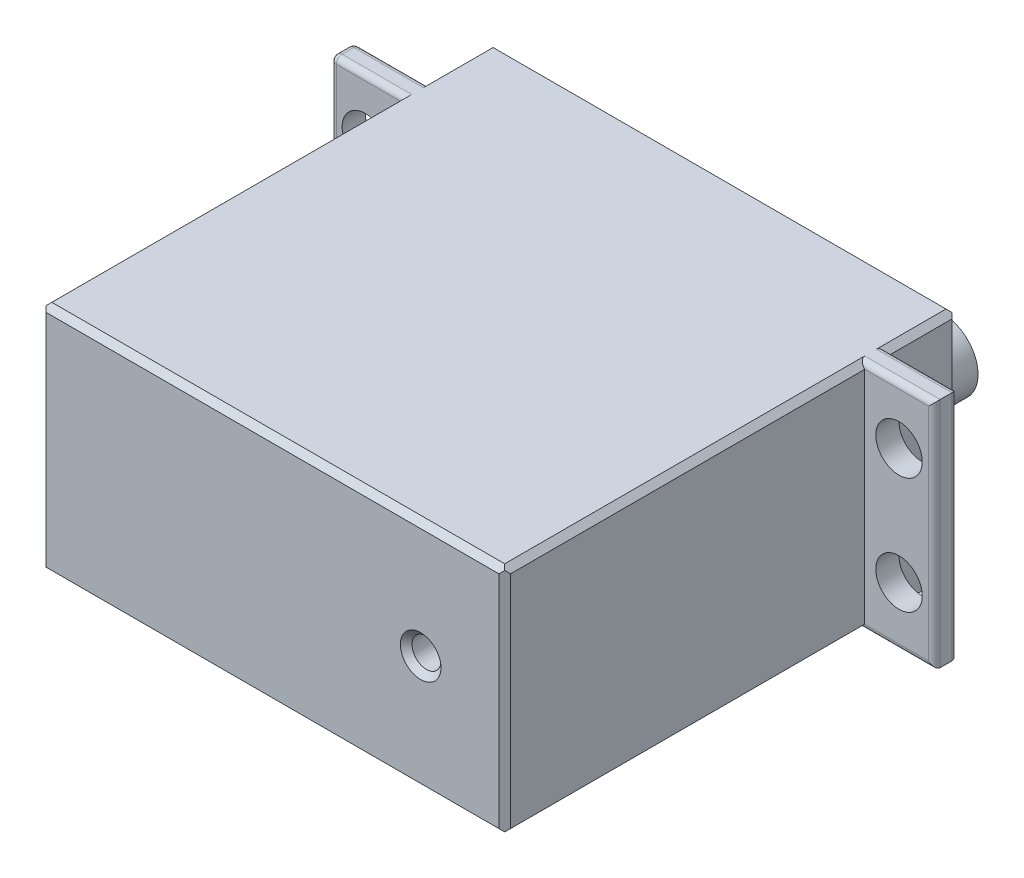
SolidWorks part; units mm, degrees
ref_plane "前视基准面" through (0, 0, 0) normal (0, 0, 1) x (1, 0, 0)
ref_plane "上视基准面" through (0, 0, 0) normal (0, 1, 0) x (1, 0, 0)
ref_plane "右视基准面" through (0, 0, 0) normal (1, 0, 0) x (0, 0, -1)
sketch "草图1" plane through (0, 0, 0) normal (0, 0, 1) x (1, 0, 0)
  line L1 (-20, 10) -> (20, 10)
  line L2 (-20, 10) -> (-20, -10)
  line L3 (-20, -10) -> (20, -10)
  line L4 (20, 10) -> (20, -10)
  line L5 (-20, 10) -> (20, -10) construction
  line L6 (-20, -10) -> (20, 10) construction
  point P0 (0, 0)
extrude "凸台-拉伸1" add sketch "草图1" along normal blind 39
sketch "草图2" plane through (-20, 0, 0) normal (-1, 0, 0) x (0, 0, 1)
  line L0 (8, 10) -> (8, -10)
  line L1 (39, 10) -> (0, 10) construction
  line L2 (39, -10) -> (0, -10) construction
  line L3 (0, 10) -> (0, -10) construction
  dimension "D1" = 8
extrude "拉伸-薄壁2" add sketch "草图2" along normal blind 6 thin contours L0 thin type one direction wall 2
sketch "草图10" plane through (0, 0, 0) normal (0, 0, -1) x (-1, 0, 0)
  line L0 (-26, 10) -> (-26, -10) construction
  circle A0 centre (-12.7625, 0) radius 2.9978
  dimension "D1" = 20
extrude "凸台-拉伸2" add sketch "草图10" along normal blind 6 contours A0
sketch "草图11" plane through (0, 0, 0) normal (0, 0, -1) x (-1, 0, 0)
  circle A0 centre (-12.7625, 0) radius 5.5764
extrude "凸台-拉伸3" add sketch "草图11" along normal blind 1
sketch "草图12" plane through (0, 0, 0) normal (0, 0, -1) x (-1, 0, 0)
  circle A0 centre (-12.7625, 0) radius 4.8827
extrude "凸台-拉伸4" add sketch "草图12" along normal blind 1.5
hole_wizard "M3 螺纹孔2" positions "3D草图2" profile "草图14" tap size "M3" standard "GB" end condition up to next
sketch3d "3D草图2"
  line L0 (12.7625, 0, -1.5) -> (12.7625, 0, -1) construction
  line L1 (12.7625, 0, -1) -> (12.7625, 0, 0) construction
  line L2 (12.7625, 0, -6) -> (12.7625, 0, -1.5) construction
  point P0 (12.7625, 0, -1)
  point P6 (12.7625, 0, -6)
sketch "草图14" plane through (12.7625, 0, -6) normal (1, 0, 0) x (0, 1, 0)
  line L0 (0, 0) -> (0, 45.001)
  line L1 (0, 45.001) -> (1.25, 45.001)
  line L2 (1.25, 45.001) -> (1.25, 0.275)
  line L3 (1.25, 0.275) -> (1.525, 0)
  line L5 (1.525, 0) -> (0, 0)
  line L6 (-1.25, 0.275) -> (-1.525, 0) construction
  line L11 (0, -6.35) -> (0, 107.95) construction
  dimension "通孔螺纹孔钻头直径" = 2.5
  dimension "通孔螺纹孔钻头深度" = 45.001
  dimension "近端锥形沉头孔直径" = 3.05
  dimension "近端锥形沉头孔角度" = 90
cosmetic thread "孔螺纹线4" parameters "D2"=3
chamfer "倒角5" distance 0.5 angle 45 5 edges at (0, 10, 0) (-20, 0, 0) (0, -10, 0) (20, 0, 0) (18.3388, 0, 0)
chamfer "倒角6" distance 0.5 angle 45 5 edges at (0, -10, 39) (-20, 0, 39) (0, 10, 39) (20, 0, 39) (14.0125, 0, 39)
sketch "草图17" plane through (20, 0, 0) normal (1, 0, 0) x (0, 0, -1)
  line L0 (-6, 10) -> (-6, -10)
  line L1 (-38.5, -10) -> (-0.5, -10) construction
  line L2 (-6, 10) -> (-6, -10) construction
  line L3 (-8, -10) -> (-8, 10)
  line L4 (-38.5, 10) -> (-0.5, 10) construction
  line L5 (-8, 10) -> (-8, -10) construction
extrude "拉伸-薄壁5" add sketch "草图17" along normal blind 6 thin thin type one direction wall 1.5
sketch "草图21" plane through (0, 0, 6) normal (0, 0, -1) x (-1, 0, 0)
  circle A0 centre (-22.9514, 5.0812) radius 2
  circle A1 centre (-22.9514, -4.9188) radius 2
  circle A2 centre (23, 5.0812) radius 2
  circle A3 centre (23, -4.9188) radius 2
  dimension "D1" = 10
extrude "切除-拉伸2" cut sketch "草图21" against normal blind 2
chamfer "倒角7" distance 0.5 angle 45 8 edges at (-20, -10, 23.25) (-20, -10, 3.25) (20, -10, 3.25) (20, -10, 23.25) (20, 10, 3.25) (20, 10, 23.25) (-20, 10, 3.25) (-20, 10, 23.25)
fillet "圆角1" radius 0.5 13 edges at (22.75, -10, 8) (22.75, 10, 8) (26, 0, 8) (22.75, -10, 6) (26, 0, 6) (22.75, 10, 6) (-22.75, -10, 8) (-26, 0, 8) (-26, 10, 7) (-22.75, 10, 8) (-22.75, 10, 6) (-26, 0, 6) (-22.75, -10, 6)
